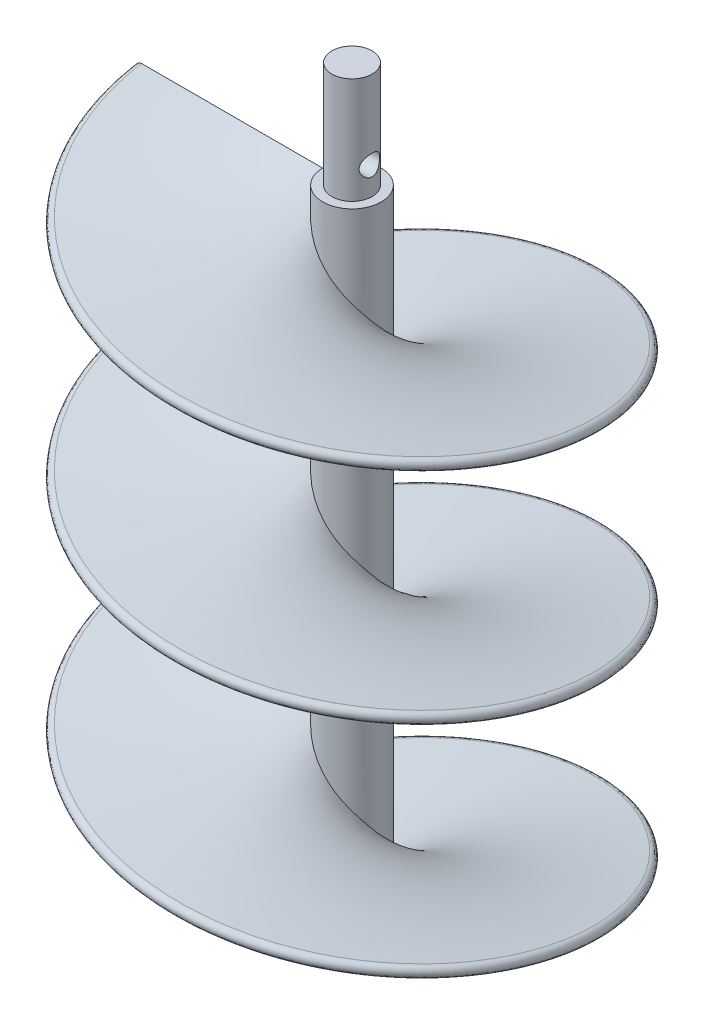
SolidWorks part; units mm, degrees
ref_plane "Front" through (0, 0, 0) normal (0, 0, 1) x (1, 0, 0)
ref_plane "Top" through (0, 0, 0) normal (0, 1, 0) x (1, 0, 0)
ref_plane "Right" through (0, 0, 0) normal (1, 0, 0) x (0, 0, -1)
sketch "Sketch2" plane through (0, 0, 0) normal (0, 1, 0) x (1, 0, 0)
  circle A0 centre (0, 0) radius 74.93
  dimension "D1" = 149.86
curve "Helix/Spiral1" pitch 76.2 height 228.6 radius 74.93 left hand yes centre (0, 0, 0) axis (0, 1, 0) start towards (0, 0, 1)
sketch "Sketch3" plane through (0, 0, 0) normal (0, 0, 1) x (1, 0, 0)
  line L0 (-73.025, 0) -> (-9.525, 0) construction
  line L1 (-73.025, 1.905) -> (-9.525, 1.905)
  line L2 (-73.025, -1.905) -> (-9.525, -1.905)
  arc A0 (-73.025, 1.905) -> (-73.025, -1.905) centre (-73.025, 0) ccw
  arc A1 (-9.525, -1.905) -> (-9.525, 1.905) centre (-9.525, 0) ccw
  point P3 (-41.275, 0)
  point P8 (-74.93, 0)
  dimension "D1" = 63.5
  dimension "D2" = 3.81
sweep "Sweep1" add profiles "Sketch3" path "Helix/Spiral1"
ref_plane "Plane1" through (0, 1.905, 0) normal (0, 1, 0) x (1, 0, 0)
sketch "Sketch4" plane through (0, 1.905, 0) normal (0, 1, 0) x (1, 0, 0)
  circle A0 centre (0, 0) radius 10.16
  dimension "D1" = 20.32
extrude "Boss-Extrude1" add sketch "Sketch4" along normal up to vertex (228.6 mm away) up to point (-9.525, 230.505, 0)
sketch "Sketch7" plane through (0, 1.905, 0) normal (0, -1, 0) x (1, 0, 0)
  circle A2 centre (0, 0) radius 10.16
extrude "Cut-Extrude3" cut sketch "Sketch7" along normal up to vertex (3.81 mm away) up to point (-9.525, -1.905, 0)
sketch "Sketch9" plane through (0, 1.905, 0) normal (0, -1, 0) x (1, 0, 0)
  circle A2 centre (0, 0) radius 7.62
  dimension "D1" = 15.24
extrude "Cut-Extrude5" cut sketch "Sketch9" against normal blind 38.1
sketch "Sketch11" plane through (0, 230.505, 0) normal (0, 1, 0) x (1, 0, 0)
  circle A0 centre (0, 0) radius 6.985
  dimension "D1" = 13.97
extrude "Boss-Extrude2" add sketch "Sketch11" along normal blind 36.83
sketch "Sketch10" plane through (0, 0, 0) normal (1, 0, 0) x (0, 0, -1)
  line L0 (-10.16, 1.905) -> (10.16, 1.905) construction
  line L1 (10.16, 230.505) -> (-10.16, 230.505) construction
  circle A0 centre (0, 11.43) radius 3.556
  circle A1 centre (0, 240.03) radius 3.556
  point P7 (0, 0)
  dimension "D1" = 7.112
  dimension "D2" = 9.525
  dimension "D3" = 9.525
extrude "Cut-Extrude6" cut sketch "Sketch10" against normal up to next and the other way up to next
